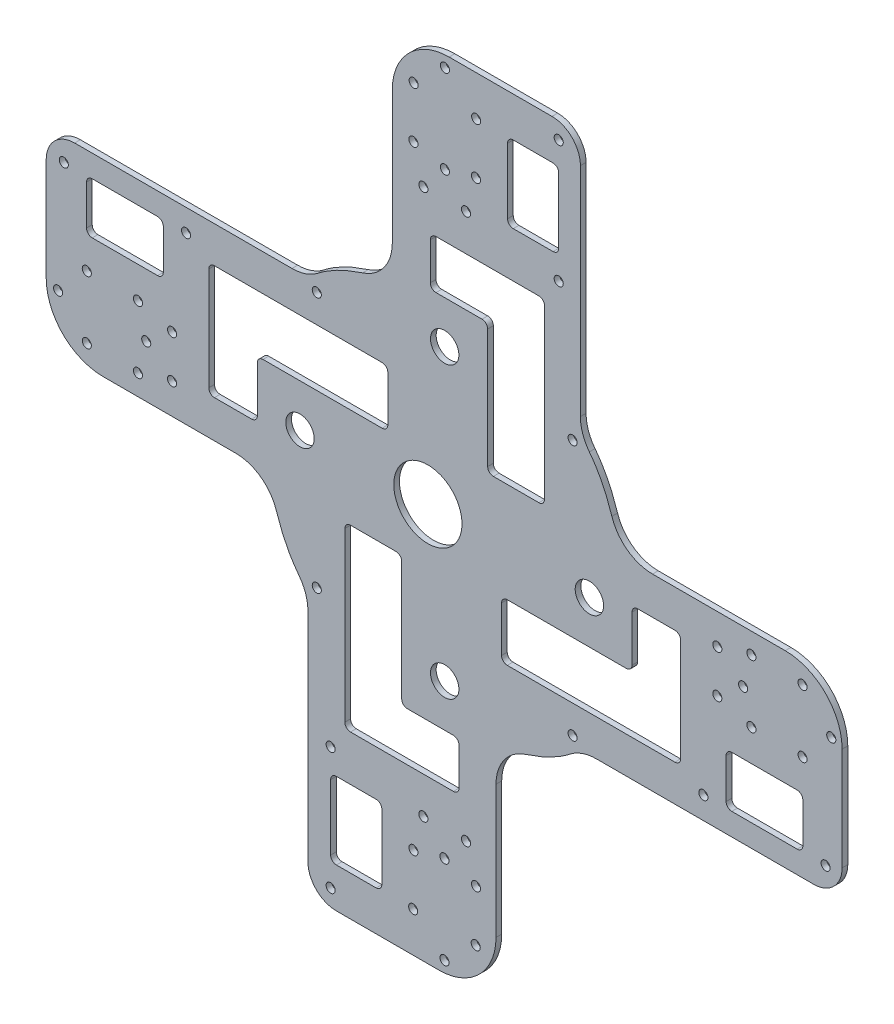
SolidWorks part; units mm, degrees
ref_plane "Front Plane" through (0, 0, 0) normal (0, 0, 1) x (1, 0, 0)
ref_plane "Top Plane" through (0, 0, 0) normal (0, 1, 0) x (1, 0, 0)
ref_plane "Right Plane" through (0, 0, 0) normal (1, 0, 0) x (0, 0, -1)
sketch "Sketch1" plane through (0, 0, 0) normal (0, 0, 1) x (1, 0, 0)
  line L0 (5.7247, 49.3016) -> (5.7247, -49.3016) construction
  line L1 (-67.5786, -18.245) -> (-114.2753, -18.245)
  line L2 (23.9697, -73.3033) -> (23.9697, -120)
  line L3 (-42.2074, -53.5469) -> (-42.2074, -130)
  line L4 (-32.2074, -140) -> (3.9697, -140)
  line L5 (55.0263, 0) -> (-43.5768, 0) construction
  line L6 (5.7247, 0) -> (53.6568, 47.9321) construction
  line L7 (5.7247, 0) -> (-42.2074, 47.9321) construction
  line L8 (5.7247, 0) -> (53.6568, -47.9321) construction
  line L9 (5.7247, 0) -> (-42.2074, -47.9321) construction
  line L10 (-47.8222, 47.9321) -> (-124.2753, 47.9321)
  line L11 (-134.2753, 37.9321) -> (-134.2753, 1.755)
  line L12 (-12.5202, 73.3033) -> (-12.5202, 120)
  line L13 (53.6568, 53.5469) -> (53.6568, 130)
  line L14 (43.6568, 140) -> (7.4798, 140)
  line L15 (79.028, 18.245) -> (125.7247, 18.245)
  line L16 (59.2716, -47.9321) -> (135.7247, -47.9321)
  line L17 (145.7247, -37.9321) -> (145.7247, -1.755)
  arc A0 (23.9697, -120) -> (3.9697, -140) centre (3.9697, -120) cw
  arc A1 (-42.2074, -130) -> (-32.2074, -140) centre (-32.2074, -130) ccw
  arc A2 (-114.2753, -18.245) -> (-134.2753, 1.755) centre (-114.2753, 1.755) cw
  arc A3 (-124.2753, 47.9321) -> (-134.2753, 37.9321) centre (-124.2753, 37.9321) ccw
  arc A4 (-12.5202, 120) -> (7.4798, 140) centre (7.4798, 120) cw
  arc A5 (53.6568, 130) -> (43.6568, 140) centre (43.6568, 130) ccw
  arc A6 (125.7247, 18.245) -> (145.7247, -1.755) centre (125.7247, -1.755) cw
  arc A7 (135.7247, -47.9321) -> (145.7247, -37.9321) centre (135.7247, -37.9321) ccw
  arc A8 (64.7348, 28.695) -> (79.028, 18.245) centre (79.028, 33.245) ccw
  arc A9 (-22.9703, 59.01) -> (-12.5202, 73.3033) centre (-27.5202, 73.3033) ccw
  arc A10 (-42.2074, -53.5469) -> (-45.3525, -44.3566) centre (-57.2074, -53.5469) ccw
  arc A11 (-53.2853, -28.695) -> (-67.5786, -18.245) centre (-67.5786, -33.245) ccw
  arc A12 (23.9697, -73.3033) -> (34.4197, -59.01) centre (38.9697, -73.3033) cw
  arc A13 (59.2716, -47.9321) -> (50.0813, -51.0772) centre (59.2716, -62.9321) ccw
  arc A14 (56.8019, 44.3566) -> (53.6568, 53.5469) centre (68.6568, 53.5469) cw
  arc A15 (-38.6319, 51.0772) -> (-47.8222, 47.9321) centre (-47.8222, 62.9321) cw
  spline S0 degree 3 poles (64.7348, 28.695) (63.545, 32.4325) (61.2168, 37.9464) (58.0546, 42.7407) (56.8019, 44.3566) knots 0.192587 0.192587 0.192587 0.192587 0.221294 0.23742 0.23742 0.23742 0.23742
  spline S1 degree 3 poles (34.4197, -59.01) (38.1573, -57.8203) (43.6711, -55.4921) (48.4655, -52.3299) (50.0813, -51.0772) knots 0.942587 0.942587 0.942587 0.942587 0.971294 0.98742 0.98742 0.98742 0.98742
  spline S2 degree 3 poles (-53.2853, -28.695) (-52.8877, -29.9441) (-50.8724, -35.6733) (-48.0897, -40.8257) (-45.3525, -44.3566) knots 0.692587 0.692587 0.692587 0.692587 0.702181 0.73742 0.73742 0.73742 0.73742
  spline S3 degree 3 poles (-22.9703, 59.01) (-26.7078, 57.8203) (-32.2217, 55.4921) (-37.016, 52.3299) (-38.6319, 51.0772) knots 0.442587 0.442587 0.442587 0.442587 0.471294 0.48742 0.48742 0.48742 0.48742
  point P9 (5.7247, 62.9443)
  point P13 (68.669, 0)
  point P15 (5.7247, -62.9443)
  point P17 (-57.2196, 0)
  point P19 (5.7247, 0)
  point P56 (5.7247, 0)
  dimension "D1" = 20
  dimension "D2" = 10
  dimension "D4" = 15
  dimension "D5" = 15
  dimension "D6" = 15
  dimension "D7" = 15
  dimension "D3" = 4
extrude "Boss-Extrude1" add sketch "Sketch1" along normal blind 2
sketch "Sketch2" plane through (0, 0, 0) normal (0, 0, -1) x (-1, 0, 0)
  circle A0 centre (0, 0) radius 12
extrude "Cut-Extrude1" cut sketch "Sketch2" against normal blind 2
sketch "Sketch3" plane through (0, 0, 0) normal (0, 0, -1) x (-1, 0, 0)
  line L0 (0, 0) -> (45, 0) construction
  line L1 (45, 0) -> (-5.9117, 50.9117) construction
  line L2 (-5.9117, 50.9117) -> (-56.8234, 0) construction
  line L3 (-56.8234, 0) -> (-5.9117, -50.9117) construction
  line L4 (-5.9117, -50.9117) -> (45, 0) construction
  circle A0 centre (-5.9117, 50.9117) radius 5
  circle A1 centre (45, 0) radius 5
  circle A2 centre (-5.9117, -50.9117) radius 5
  circle A3 centre (-56.8234, 0) radius 5
extrude "Cut-Extrude2" cut sketch "Sketch3" against normal blind 2
ref_axis "Axis1" through (5.9117, 50.9117, 2) along (0, 0, -1)
ref_axis "Axis2" through (-45, 0, 2) along (0, 0, -1)
ref_axis "Axis3" through (5.9117, -50.9117, 2) along (0, 0, -1)
ref_axis "Axis4" through (56.8234, 0, 2) along (0, 0, -1)
sketch "Sketch6" plane through (0, 0, 0) normal (0, 0, -1) x (-1, 0, 0)
  line L9 (97, 0) -> (-108.8234, 0) construction
  line L10 (97, -8) -> (97, 8) construction
  line L11 (-108.8234, 8) -> (-108.8234, -8) construction
  circle A0 centre (34.2074, -134) radius 1.6
  circle A1 centre (34.2074, -91) radius 1.6
  circle A2 centre (5.1695, -125.9117) radius 1.6
  circle A3 centre (5.0884, -107.9117) radius 1.6
  circle A4 centre (-16.8306, -125.9117) radius 1.6
  circle A5 centre (-16.9117, -107.9117) radius 1.6
  circle A6 centre (-13.4117, -95.9117) radius 1.6
  circle A7 centre (1.5883, -95.9117) radius 1.6
  circle A8 centre (39.0883, -45) radius 1.6
  circle A9 centre (-50.9117, -45) radius 1.6
  circle A10 centre (-50.9117, 45) radius 1.6
  circle A11 centre (39.0883, 45) radius 1.6
  circle A12 centre (-139.9117, -40.119) radius 1.6
  circle A13 centre (-96.9117, -40.119) radius 1.6
  circle A14 centre (-131.8234, -11.0812) radius 1.6
  circle A15 centre (-113.8234, -11.0001) radius 1.6
  circle A16 centre (-131.8234, 10.9189) radius 1.6
  circle A17 centre (-113.8234, 11) radius 1.6
  circle A18 centre (-101.8234, 7.5) radius 1.6
  circle A19 centre (-101.8234, -7.5) radius 1.6
  circle A20 centre (-46.0307, 134) radius 1.6
  circle A21 centre (-46.0307, 91) radius 1.6
  circle A22 centre (-16.9929, 125.9117) radius 1.6
  circle A23 centre (-16.9118, 107.9117) radius 1.6
  circle A24 centre (5.0072, 125.9117) radius 1.6
  circle A25 centre (5.0883, 107.9117) radius 1.6
  circle A26 centre (1.5883, 95.9117) radius 1.6
  circle A27 centre (-13.4117, 95.9117) radius 1.6
  circle A28 centre (128.0883, 40.119) radius 1.6
  circle A29 centre (85.0883, 40.119) radius 1.6
  circle A30 centre (120, 11.0812) radius 1.6
  circle A31 centre (102, 11.0001) radius 1.6
  circle A32 centre (120, -10.9189) radius 1.6
  circle A33 centre (102, -11) radius 1.6
  circle A34 centre (90, -7.5) radius 1.6
  circle A35 centre (90, 7.5) radius 1.6
  point P26 (-5.9117, 0)
  point P84 (-5.9117, 0)
  dimension "D1" = 4
extrude "Cut-Extrude3" cut sketch "Sketch6" against normal blind 2
ref_axis "Axis5" through (-34.2074, -134, 2) along (0, 0, -1)
sketch "Sketch7" plane through (0, 0, 2) normal (0, 0, 1) x (1, 0, 0)
  line L0 (-29.2074, -65.9117) -> (-29.2074, -81)
  line L1 (-32.2074, -99) -> (-18.2074, -99)
  line L2 (-34.2074, -101) -> (-34.2074, -124)
  line L3 (-32.2074, -126) -> (-18.2074, -126)
  line L4 (-16.2074, -101) -> (-16.2074, -124)
  line L5 (-27.2074, -83) -> (8.9697, -83)
  line L8 (10.9697, -81) -> (10.9697, -67.9117)
  line L10 (-29.2074, -65.9117) -> (-29.2074, -22)
  line L11 (-27.2074, -20) -> (-11.2074, -20)
  line L12 (-9.2074, -63.9117) -> (-9.2074, -22)
  line L13 (-60, 35.119) -> (-75.0883, 35.119)
  line L14 (-7.2074, -65.9117) -> (8.9697, -65.9117)
  line L15 (-77.0883, 33.119) -> (-77.0883, -3.058)
  line L16 (-75.0883, -5.058) -> (-62, -5.058)
  line L17 (-60, 35.119) -> (-16.0883, 35.119)
  line L18 (-14.0883, 33.119) -> (-14.0883, 17.119)
  line L19 (-58, 15.119) -> (-16.0883, 15.119)
  line L20 (-60, 13.119) -> (-60, -3.058)
  line L21 (41.0307, 65.9117) -> (41.0307, 81)
  line L22 (39.0307, 83) -> (2.8537, 83)
  line L23 (0.8537, 81) -> (0.8537, 67.9117)
  line L24 (41.0307, 65.9117) -> (41.0307, 22)
  line L25 (39.0307, 20) -> (23.0307, 20)
  line L26 (21.0307, 63.9117) -> (21.0307, 22)
  line L27 (19.0307, 65.9117) -> (2.8537, 65.9117)
  line L28 (71.8234, -35.119) -> (86.9117, -35.119)
  line L29 (88.9117, -33.119) -> (88.9117, 3.058)
  line L30 (86.9117, 5.058) -> (73.8234, 5.058)
  line L31 (71.8234, -35.119) -> (27.9117, -35.119)
  line L32 (25.9117, -33.119) -> (25.9117, -17.119)
  line L33 (69.8234, -15.119) -> (27.9117, -15.119)
  line L34 (71.8234, -13.119) -> (71.8234, 3.058)
  line L35 (-93.0883, 38.119) -> (-93.0883, 24.119)
  line L36 (-95.0883, 40.119) -> (-118.0883, 40.119)
  line L37 (-120.0883, 38.119) -> (-120.0883, 24.119)
  line L38 (-95.0883, 22.119) -> (-118.0883, 22.119)
  line L39 (44.0307, 99) -> (30.0307, 99)
  line L40 (46.0307, 101) -> (46.0307, 124)
  line L41 (44.0307, 126) -> (30.0307, 126)
  line L42 (28.0307, 101) -> (28.0307, 124)
  line L43 (104.9117, -38.119) -> (104.9117, -24.119)
  line L44 (106.9117, -40.119) -> (129.9117, -40.119)
  line L45 (131.9117, -38.119) -> (131.9117, -24.119)
  line L46 (106.9117, -22.119) -> (129.9117, -22.119)
  arc A0 (69.8234, -15.119) -> (71.8234, -13.119) centre (69.8234, -13.119) ccw
  arc A1 (-34.2074, -124) -> (-32.2074, -126) centre (-32.2074, -124) ccw
  arc A2 (-18.2074, -126) -> (-16.2074, -124) centre (-18.2074, -124) ccw
  arc A3 (-18.2074, -99) -> (-16.2074, -101) centre (-18.2074, -101) cw
  arc A4 (-32.2074, -99) -> (-34.2074, -101) centre (-32.2074, -101) ccw
  arc A5 (27.9117, -35.119) -> (25.9117, -33.119) centre (27.9117, -33.119) cw
  arc A6 (25.9117, -17.119) -> (27.9117, -15.119) centre (27.9117, -17.119) cw
  arc A7 (88.9117, 3.058) -> (86.9117, 5.058) centre (86.9117, 3.058) ccw
  arc A8 (73.8234, 5.058) -> (71.8234, 3.058) centre (73.8234, 3.058) ccw
  arc A9 (86.9117, -35.119) -> (88.9117, -33.119) centre (86.9117, -33.119) ccw
  arc A10 (21.0307, 63.9117) -> (19.0307, 65.9117) centre (19.0307, 63.9117) ccw
  arc A11 (41.0307, 22) -> (39.0307, 20) centre (39.0307, 22) cw
  arc A12 (23.0307, 20) -> (21.0307, 22) centre (23.0307, 22) cw
  arc A13 (2.8537, 83) -> (0.8537, 81) centre (2.8537, 81) ccw
  arc A14 (0.8537, 67.9117) -> (2.8537, 65.9117) centre (2.8537, 67.9117) ccw
  arc A15 (41.0307, 81) -> (39.0307, 83) centre (39.0307, 81) ccw
  arc A16 (-58, 15.119) -> (-60, 13.119) centre (-58, 13.119) ccw
  arc A17 (-16.0883, 35.119) -> (-14.0883, 33.119) centre (-16.0883, 33.119) cw
  arc A18 (-14.0883, 17.119) -> (-16.0883, 15.119) centre (-16.0883, 17.119) cw
  arc A19 (-77.0883, -3.058) -> (-75.0883, -5.058) centre (-75.0883, -3.058) ccw
  arc A20 (-62, -5.058) -> (-60, -3.058) centre (-62, -3.058) ccw
  arc A21 (-75.0883, 35.119) -> (-77.0883, 33.119) centre (-75.0883, 33.119) ccw
  arc A22 (-7.2074, -65.9117) -> (-9.2074, -63.9117) centre (-7.2074, -63.9117) cw
  arc A23 (-29.2074, -22) -> (-27.2074, -20) centre (-27.2074, -22) cw
  arc A24 (-11.2074, -20) -> (-9.2074, -22) centre (-11.2074, -22) cw
  arc A25 (8.9697, -83) -> (10.9697, -81) centre (8.9697, -81) ccw
  arc A26 (8.9697, -65.9117) -> (10.9697, -67.9117) centre (8.9697, -67.9117) cw
  arc A27 (-29.2074, -81) -> (-27.2074, -83) centre (-27.2074, -81) ccw
  arc A28 (-118.0883, 40.119) -> (-120.0883, 38.119) centre (-118.0883, 38.119) ccw
  arc A29 (-120.0883, 24.119) -> (-118.0883, 22.119) centre (-118.0883, 24.119) ccw
  arc A30 (-93.0883, 24.119) -> (-95.0883, 22.119) centre (-95.0883, 24.119) cw
  arc A31 (-93.0883, 38.119) -> (-95.0883, 40.119) centre (-95.0883, 38.119) ccw
  arc A32 (46.0307, 124) -> (44.0307, 126) centre (44.0307, 124) ccw
  arc A33 (30.0307, 126) -> (28.0307, 124) centre (30.0307, 124) ccw
  arc A34 (30.0307, 99) -> (28.0307, 101) centre (30.0307, 101) cw
  arc A35 (44.0307, 99) -> (46.0307, 101) centre (44.0307, 101) ccw
  arc A36 (129.9117, -40.119) -> (131.9117, -38.119) centre (129.9117, -38.119) ccw
  arc A37 (131.9117, -24.119) -> (129.9117, -22.119) centre (129.9117, -24.119) ccw
  arc A38 (104.9117, -24.119) -> (106.9117, -22.119) centre (106.9117, -24.119) cw
  arc A39 (104.9117, -38.119) -> (106.9117, -40.119) centre (106.9117, -38.119) ccw
  point P16 (5.9117, 0)
  point P46 (5.9117, 0)
  point P131 (5.9117, 0)
  dimension "D1" = 2
  dimension "D3" = 2
  dimension "D2" = 4
  dimension "D4" = 4
extrude "Cut-Extrude4" cut sketch "Sketch7" against normal blind 2
sketch "Sketch8" plane through (0, 0, 2) normal (0, 0, 1) x (1, 0, 0)
  circle A0 centre (5.8305, -105) radius 1.6
  circle A1 centre (5.8305, -136) radius 1.6
  circle A2 centre (-99.0883, 0.0811) radius 1.6
  circle A3 centre (-130.0883, 0.0811) radius 1.6
  circle A4 centre (5.9928, 105) radius 1.6
  circle A5 centre (5.9928, 136) radius 1.6
  circle A6 centre (110.9117, -0.0811) radius 1.6
  circle A7 centre (141.9117, -0.0811) radius 1.6
  point P10 (5.9117, 0)
  point P24 (5.9117, 0)
  dimension "D1" = 4
extrude "Cut-Extrude5" cut sketch "Sketch8" against normal blind 2
